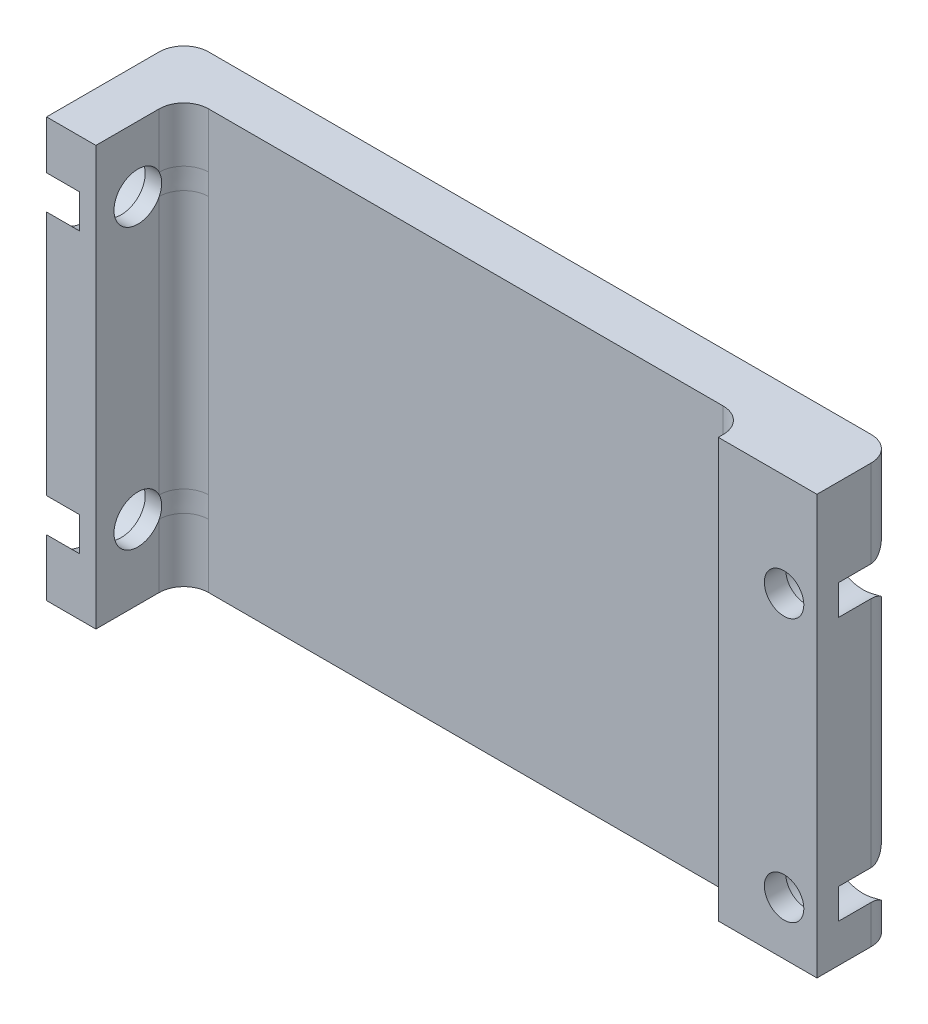
SolidWorks part; units mm, degrees
ref_plane "Plano frontal" through (0, 0, 0) normal (0, 0, 1) x (1, 0, 0)
ref_plane "Plano superior" through (0, 0, 0) normal (0, 1, 0) x (1, 0, 0)
ref_plane "Plano direito" through (0, 0, 0) normal (1, 0, 0) x (0, 0, -1)
sketch "Esboço2" plane through (0, 0, -1) normal (0, 0, 1) x (1, 0, 0)
  line L0 (-31.75, -14.525) -> (-29.25, -14.525) construction
  line L6 (0.3, -40) -> (6.3, -40)
  line L7 (0.3, -40) -> (0.3, -14.525)
  line L8 (0.3, -14.525) -> (6.3, -14.525)
  line L9 (6.3, -40) -> (6.3, -14.525)
  line L11 (4.8, -40) -> (2.8, -40) construction
  circle A1 centre (4.3, -12.75) radius 1.25 construction
  circle A2 centre (4.3, -20.75) radius 1.25 construction
  dimension "D2" = 4
  dimension "D1" = 2
extrude "Ressalto-extrusão2" add sketch "Esboço2" against normal up to surface (1.8 mm away)
sketch "Esboço3" plane through (0, 0, -2.8) normal (0, 0, -1) x (-1, 0, 0)
  line L0 (33.75, 0) -> (33.75, -38.6) construction
  line L1 (-6.3, -14.525) -> (34, -14.525)
  line L2 (-6.3, -14.525) -> (-6.3, -40)
  line L3 (-6.3, -40) -> (34, -40)
  line L4 (34, -14.525) -> (34, -40)
  line L5 (-6.3, -40) -> (-0.3, -40) construction
  dimension "D1" = 0.25
extrude "Ressalto-extrusão3" add sketch "Esboço3" along normal blind 3
sketch "Esboço4" plane through (-34, 0, 0) normal (-1, 0, 0) x (0, 0, 1)
  line L1 (-5.8, -40) -> (2.55, -40)
  line L2 (-5.8, -40) -> (-5.8, -14.525)
  line L3 (-5.8, -14.525) -> (2.55, -14.525)
  line L4 (2.55, -40) -> (2.55, -14.525)
  line L5 (-5.8, -14.525) -> (-2.8, -14.525) construction
  dimension "D1" = 0.25
extrude "Ressalto-extrusão4" add sketch "Esboço4" along normal blind 3
hole_wizard "CBORE for M2.5 SHCS2" positions "3DSketch1" profile "Sketch1" counterbore size "M2.5" standard "ANSI Metric"
sketch3d "3DSketch1"
  circle A1 centre (-33.75, -18.5, 0) radius 1.35 construction
  circle A2 centre (-31.25, -35.5, 0) radius 1.35 construction
  point P8 (-37, -18.5, 0)
  point P20 (-32.4, -18.5, 0)
  point P21 (-37, -35.5, 0)
  point P26 (-29.9, -35.5, 0)
sketch "Sketch1" plane through (-37, -18.5, 0) normal (0, 1, 0) x (0, 0, 1)
  line L0 (0, 0) -> (0, 3.8712)
  line L1 (0, 3.8712) -> (1.45, 3)
  line L2 (1.45, 3) -> (1.45, 2)
  line L3 (1.45, 2) -> (2.75, 2)
  line L4 (2.75, 2) -> (2.75, 0)
  line L5 (2.75, 0) -> (0, 0)
  line L10 (0, 3.8712) -> (-1.45, 3) construction
  line L11 (0, -6.35) -> (0, 107.95) construction
  dimension "Hole Dia." = 2.9
  dimension "Hole Depth" = 3
  dimension "C'Bore Dia." = 5.5
  dimension "C'Bore Depth" = 2
  dimension "Drill Angle" = 118
hole_wizard "Rebaixo para parafuso com cabeça redonda de M21" positions "Esboço5" profile "Esboço6" counterbore size "M2" standard "DIN" end condition up to next
sketch "Esboço5" plane through (0, 0, -5.8) normal (0, 0, -1) x (-1, 0, 0)
  circle A2 centre (-4.3, -36.75) radius 1.25 construction
  circle A3 centre (-4.3, -20.75) radius 1.25 construction
  point P15 (-4.3, -36.75)
  point P17 (-4.3, -20.75)
sketch "Esboço6" plane through (4.3, -36.75, -5.8) normal (1, 0, 0) x (0, 1, 0)
  line L0 (0, 0) -> (0, 4.8)
  line L1 (0, 4.8) -> (1.2, 4.8)
  line L3 (1.2, 4.8) -> (1.2, 3.5)
  line L4 (1.2, 3.5) -> (2.2, 3.5)
  line L5 (2.2, 3.5) -> (2.2, 0)
  line L7 (2.2, 0) -> (0, 0)
  line L11 (0, -6.35) -> (0, 107.95) construction
  dimension "Thru Hole Dia." = 2.4
  dimension "Thru Hole Depth" = 4.8
  dimension "C'Bore Dia." = 4.4
  dimension "C'Bore Depth" = 3.5
fillet "Filete1" radius 1.5 6 edges at (6.3, -38.8333, -5.8) (6.3, -28.75, -5.8) (6.3, -17.1792, -5.8) (0.3, -27.2625, -2.8) (-34, -27.2625, -2.8) (-37, -27.2625, -5.8)
